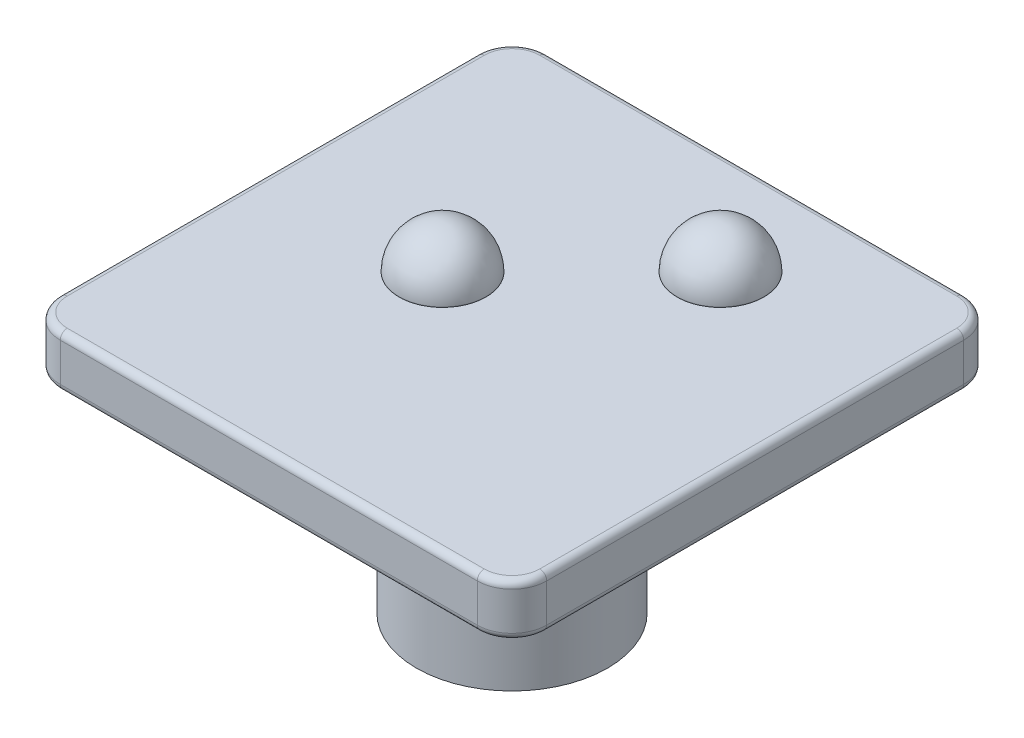
SolidWorks part; units mm, degrees
ref_plane "Front Plane" through (0, 0, 0) normal (0, 0, 1) x (1, 0, 0)
ref_plane "Top Plane" through (0, 0, 0) normal (0, 1, 0) x (1, 0, 0)
ref_plane "Right Plane" through (0, 0, 0) normal (1, 0, 0) x (0, 0, -1)
sketch "Sketch1" plane through (0, 0, 0) normal (0, 1, 0) x (1, 0, 0)
  line L1 (-7.3247, 4.3967) -> (4.6753, 4.3967)
  line L2 (-8.3247, 3.3967) -> (-8.3247, -8.6033)
  line L3 (-7.3247, -9.6033) -> (4.6753, -9.6033)
  line L4 (5.6753, 3.3967) -> (5.6753, -8.6033)
  arc A0 (-8.3247, -8.6033) -> (-7.3247, -9.6033) centre (-7.3247, -8.6033) ccw
  arc A1 (4.6753, -9.6033) -> (5.6753, -8.6033) centre (4.6753, -8.6033) ccw
  arc A2 (4.6753, 4.3967) -> (5.6753, 3.3967) centre (4.6753, 3.3967) cw
  arc A3 (-7.3247, 4.3967) -> (-8.3247, 3.3967) centre (-7.3247, 3.3967) ccw
  point P8 (5.6753, -9.6033)
  point P11 (5.6753, 4.3967)
  point P14 (-8.3247, 4.3967)
  dimension "D3" = 1
  dimension "D1" = 14
  dimension "D2" = 14
extrude "Boss-Extrude1" add sketch "Sketch1" along normal blind 1.5
sketch "Sketch2" plane through (0, 0, 0) normal (0, -1, 0) x (1, 0, 0)
  line L0 (-7.3247, 9.6033) -> (4.6753, 9.6033) construction
  line L1 (5.6753, 8.6033) -> (5.6753, -3.3967) construction
  line L2 (-1.3247, -4.3967) -> (-1.3247, 9.6033) construction
  line L3 (-8.3247, 2.6033) -> (5.6753, 2.6033) construction
  line L4 (-8.3247, -3.3967) -> (-8.3247, 8.6033) construction
  circle A0 centre (-1.3247, 2.6033) radius 2.75
  dimension "D1" = 7
  dimension "D2" = 7
extrude "Boss-Extrude2" add sketch "Sketch2" along normal blind 6
sketch "Sketch3" plane through (0, -6, 0) normal (0, -1, 0) x (1, 0, 0)
  line L0 (-1.3247, 5.3533) -> (-1.3247, -0.1467) construction
  line L1 (-3.3247, 3.1533) -> (0.6753, 3.1533)
  line L2 (-3.3247, 3.1533) -> (-3.3247, 2.0533)
  line L3 (-3.3247, 2.0533) -> (0.6753, 2.0533)
  line L4 (0.6753, 3.1533) -> (0.6753, 2.0533)
  line L5 (-1.8747, 4.6033) -> (-0.7747, 4.6033)
  line L6 (-1.8747, 4.6033) -> (-1.8747, 0.6033)
  line L7 (-1.8747, 0.6033) -> (-0.7747, 0.6033)
  line L8 (-0.7747, 4.6033) -> (-0.7747, 0.6033)
  line L9 (-4.0747, 2.6033) -> (1.4253, 2.6033) construction
  circle A3 centre (-1.3247, 2.6033) radius 2.75 construction
  circle A4 centre (-1.3247, 2.6033) radius 2.75 construction
  dimension "D7" = 0.55
  dimension "D1" = 4
  dimension "D2" = 1.1
  dimension "D3" = 1.1
  dimension "D4" = 4
  dimension "D8" = 0.55
extrude "Cut-Extrude1" cut sketch "Sketch3" against normal blind 6 contours L8 L5 L6 L1 | L1 L8 L3 L4 | L8 L1 L6 L3 | L6 L1 L2 L3 | L8 L3 L6 L7 region at (-2.5997, -6, 2.6033) region at (-1.3247, -6, 3.8783) region at (-1.3247, -6, 2.6033) region at (-0.0497, -6, 2.6033) region at (-1.3247, -6, 1.3283)
chamfer "Chamfer1" distance 0.3 angle 45 12 edges at (-1.3247, -6, 0.6033) (-1.8747, -6, 1.3283) (-2.5997, -6, 2.0533) (-3.3247, -6, 2.6033) (-2.5997, -6, 3.1533) (-0.7747, -6, 1.3283) (-0.0497, -6, 2.0533) (0.6753, -6, 2.6033) (-0.0497, -6, 3.1533) (-0.7747, -6, 3.8783) (-1.3247, -6, 4.6033) (-1.8747, -6, 3.8783)
fillet "Fillet1" radius 1 1 edges at (-1.3247, 0, -0.1467)
sketch "Sketch4" plane through (0, 1.5, 0) normal (0, 1, 0) x (1, 0, 0)
  line L0 (-1.3247, 4.3967) -> (-1.3247, -9.6033) construction
  line L1 (4.6753, 4.3967) -> (-7.3247, 4.3967) construction
  line L2 (-7.3247, -9.6033) -> (4.6753, -9.6033) construction
  line L3 (5.6753, -2.6033) -> (-8.3247, -2.6033) construction
  line L4 (-8.3247, 3.3967) -> (-8.3247, -8.6033) construction
  line L5 (5.6753, -8.6033) -> (5.6753, 3.3967) construction
  line L6 (-3.3247, 4.3967) -> (-3.3247, -9.6033) construction
  line L7 (0.6753, 4.3967) -> (0.6753, -9.6033) construction
  line L8 (-8.3247, 1.3967) -> (5.6753, 1.3967) construction
  line L9 (5.6753, -6.6033) -> (-8.3247, -6.6033) construction
  circle A2 centre (-3.3247, -2.6033) radius 1.25
  circle A5 centre (0.6753, 1.3967) radius 1.25
  dimension "D1" = 4
  dimension "D2" = 4
  dimension "D3" = 2
  dimension "D4" = 2
extrude "Boss-Extrude3" add sketch "Sketch4" along normal blind 0.01
dome "Dome2" faces to dome 1 distance 1.25 reverse direction no elliptical dome no face at (0.6753, 1.51, -0.1467) parameters "D1"=1.25
dome "Dome3" faces to dome 1 distance 1.25 reverse direction no elliptical dome no face at (-3.3247, 1.51, 3.8533) parameters "D1"=1.25
fillet "Fillet3" radius 0.2 16 edges at (5.3824, 1.5, -4.1038) (5.6753, 1.5, 2.6033) (5.3824, 1.5, 9.3104) (-1.3247, 1.5, 9.6033) (-8.0318, 1.5, 9.3104) (-8.0318, 1.5, -4.1038) (-8.3247, 1.5, 2.6033) (-1.3247, 1.5, -4.3967) (5.3824, 0, 9.3104) (5.6753, 0, 2.6033) (5.3824, 0, -4.1038) (-1.3247, 0, -4.3967) (-8.0318, 0, -4.1038) (-8.3247, 0, 2.6033) (-8.0318, 0, 9.3104) (-1.3247, 0, 9.6033)
